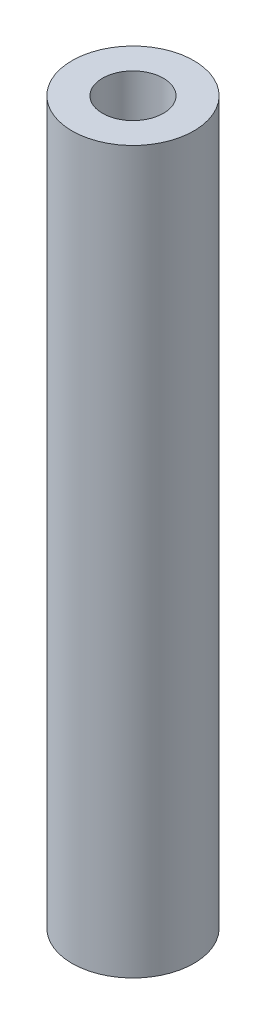
SolidWorks part; units mm, degrees
ref_plane "Front Plane" through (0, 0, 0) normal (0, 0, 1) x (1, 0, 0)
ref_plane "Top Plane" through (0, 0, 0) normal (0, 1, 0) x (1, 0, 0)
ref_plane "Right Plane" through (0, 0, 0) normal (1, 0, 0) x (0, 0, -1)
sketch "Sketch1" plane through (0, 0, 0) normal (0, 1, 0) x (1, 0, 0)
  circle A0 centre (0, 0) radius 1.5
  circle A1 centre (0, 0) radius 3
  dimension "D1" = 6
  dimension "D2" = 3
extrude "standoff" add sketch "Sketch1" along normal blind 35.5
